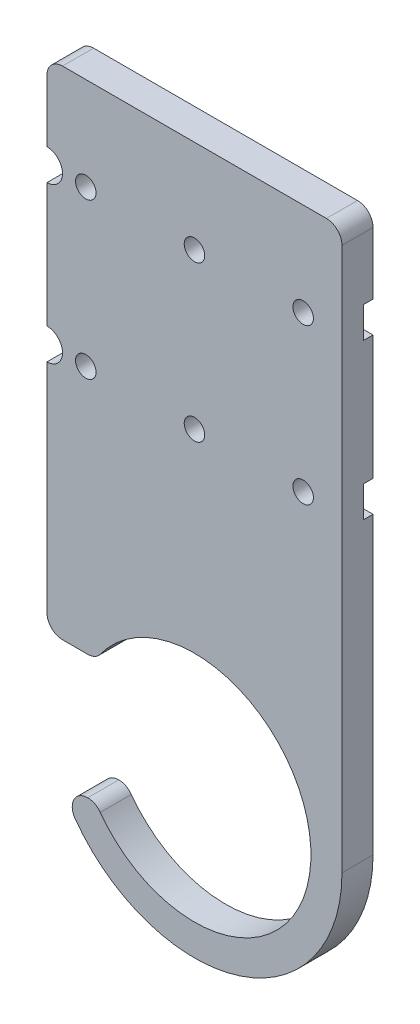
SolidWorks part; units mm, degrees
ref_plane "정면" through (0, 0, 0) normal (0, 0, 1) x (1, 0, 0)
ref_plane "윗면" through (0, 0, 0) normal (0, 1, 0) x (1, 0, 0)
ref_plane "우측면" through (0, 0, 0) normal (1, 0, 0) x (0, 0, -1)
sketch "스케치1" plane through (0, 0, 0) normal (0, 0, 1) x (1, 0, 0)
  line L0 (0, 0) -> (-88.3601, 0) construction
  line L1 (-56.6559, 20) -> (0, 20)
  line L2 (-56.6559, 20) -> (-56.6559, -20)
  line L3 (-56.6559, -20) -> (0, -20)
  line L4 (0, 20) -> (0, -20)
  line L5 (0, 210.1561) -> (0, -61.7833) construction
  line L6 (47.5, 0) -> (-47.5, 0)
  line L7 (47.5, 0) -> (47.5, 180)
  line L8 (47.5, 180) -> (-47.5, 180)
  line L9 (-47.5, 0) -> (-47.5, 180)
  line L10 (-68.3561, 100) -> (65.3348, 100) construction
  line L11 (-68.3561, 150) -> (82.2308, 150) construction
  line L12 (-47.5, 105) -> (-47.5, 95)
  line L17 (-47.5, 105) -> (47.5, 105)
  line L18 (-47.5, 95) -> (47.5, 95)
  line L19 (47.5, 105) -> (47.5, 95)
  line L20 (-47.5, 155) -> (-47.5, 145)
  line L21 (-47.5, 155) -> (47.5, 155)
  line L22 (-47.5, 145) -> (47.5, 145)
  line L23 (47.5, 155) -> (47.5, 145)
  circle A0 centre (0, 0) radius 47.5
  circle A1 centre (0, 0) radius 37.5
  circle A2 centre (-47.5, 100) radius 5
  circle A3 centre (-47.5, 150) radius 5
  circle A4 centre (-35, 100) radius 2.25
  circle A5 centre (0, 100) radius 2.3
  circle A6 centre (35, 100) radius 2
  circle A7 centre (0, 150) radius 2.25
  circle A8 centre (35, 150) radius 2.25
  circle A9 centre (-35, 150) radius 2.25
  circle A10 centre (35, 100) radius 3.3
  circle A11 centre (0, 100) radius 3.3
  circle A12 centre (-35, 100) radius 3.3
  circle A13 centre (-35, 150) radius 3.3
  circle A14 centre (0, 150) radius 3.3
  circle A15 centre (35, 150) radius 3.3
  point P27 (-47.5, 100)
  point P50 (0, 0)
  dimension "D1" = 95
  dimension "D4" = 75
  dimension "D6" = 47.5
  dimension "D7" = 95
  dimension "D10" = 10
  dimension "D11" = 10
  dimension "D12" = 4
  dimension "D13" = 4.6
  dimension "D14" = 4.5
  dimension "D17" = 4.5
  dimension "D18" = 4.5
  dimension "D19" = 4.5
  dimension "D20" = 6.6
  dimension "D23" = 6.6
  dimension "D24" = 6.6
  dimension "D25" = 6.6
  dimension "D26" = 6.6
  dimension "D27" = 6.6
  dimension "D2" = 40
  dimension "D3" = 20
  dimension "D5" = 180
  dimension "D8" = 100
  dimension "D9" = 150
  dimension "D15" = 35
  dimension "D16" = 35
  dimension "D21" = 35
  dimension "D22" = 35
extrude "보스-돌출1" add sketch "스케치1" along normal blind 10 contours A1 L3 A0 L6 | A1 L6 A0 L1 | A0 L7 L18 L9 L1 | A2 L18 L7 L17 | L22 L9 L17 L7 | A3 L22 L7 L21 | L9 L21 L7 L8 region at (0.2446, 65.4446, 0) region at (10.0203, 45.3841, 0) region at (-43.289, 95.789, 0) region at (-37.4028, -21.0228, 0) region at (0, 125, 0) region at (-43.289, 145.789, 0) region at (0, 167.5, 0)
extrude "컷-돌출1" cut sketch "스케치1<4>" along normal blind 3 contours A3 L22 L7 L21 | L18 L19 L17 L12 region at (-43.289, 145.789, 0)
sketch "스케치1<4>" plane through (0, 0, 0) normal (0, 0, 1) x (1, 0, 0) same geometry as "스케치1"
fillet "필렛4" radius 5 4 edges at (-31.7214, 20, 5) (-47.5, 20, 5) (-31.7214, -20, 5) (-43.0842, -20, 5)
fillet "필렛8" radius 5 2 edges at (47.5, 180, 5) (-47.5, 180, 5)
